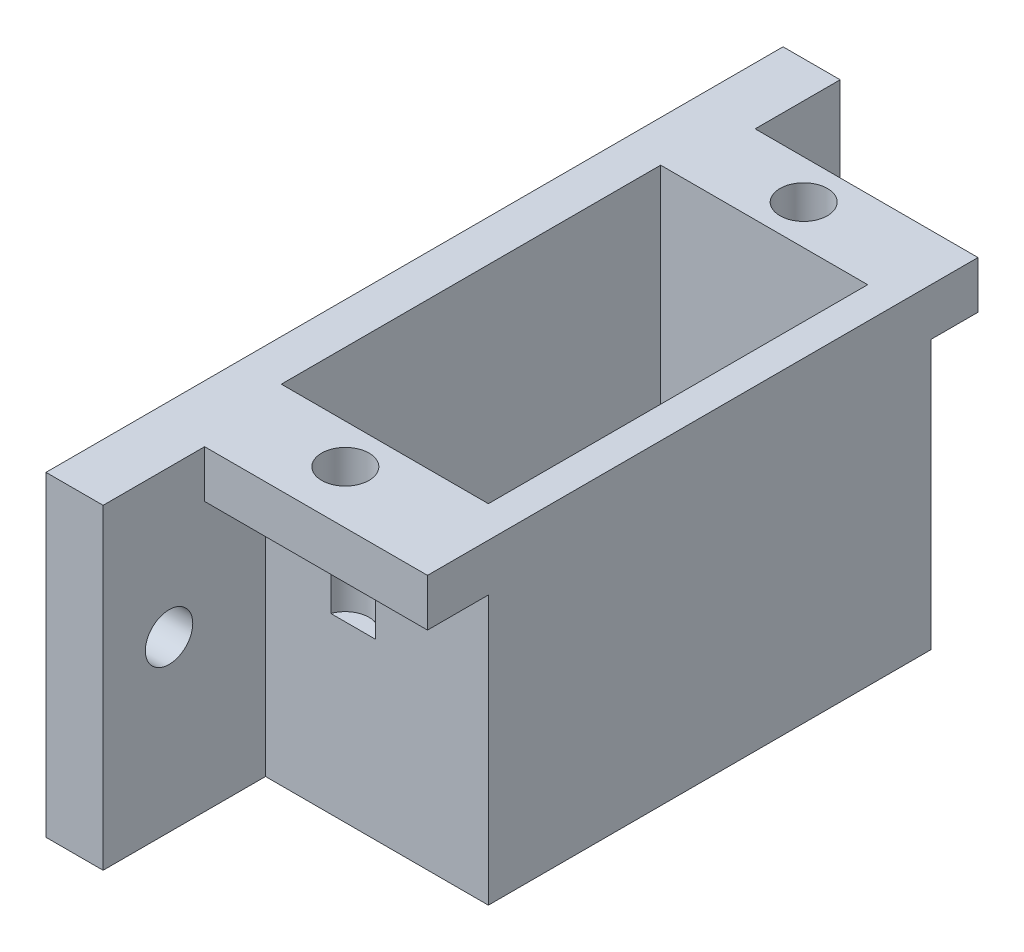
SolidWorks part; units mm, degrees
ref_plane "Płaszczyzna przednia" through (0, 0, 0) normal (0, 0, 1) x (1, 0, 0)
ref_plane "Płaszczyzna górna" through (0, 0, 0) normal (0, 1, 0) x (1, 0, 0)
ref_plane "Płaszczyzna prawa" through (0, 0, 0) normal (1, 0, 0) x (0, 0, -1)
sketch "Sketch1" plane through (0, 0, 0) normal (0, 1, 0) x (1, 0, 0)
  line L1 (51.8037, 18.5) -> (51.8037, 21.4784)
  line L3 (34.0907, 18.5) -> (37.7037, 18.5)
  line L4 (34.0907, 18.5) -> (34.0907, 26.8576)
  line L5 (34.0907, 26.8576) -> (37.7037, 26.8576)
  line L6 (34.0907, 18.5) -> (51.8037, 18.5)
  line L7 (36.7037, 16.5) -> (49.8037, 16.5)
  line L8 (36.7037, 16.5) -> (36.7037, -7.5)
  line L9 (36.7037, -7.5) -> (49.8037, -7.5)
  line L10 (49.8037, 16.5) -> (49.8037, -7.5)
  line L11 (51.8037, 18.5) -> (51.8037, -9.5)
  line L12 (34.0907, -9.5) -> (51.8037, -9.5)
  line L13 (34.0907, 18.5) -> (34.0907, -9.5)
  line L14 (37.7037, 18.5) -> (37.7037, 26.8576)
  line L15 (34.0907, -9.5) -> (37.7037, -9.5)
  line L16 (34.0907, -9.5) -> (34.0907, -19.7762)
  line L17 (34.0907, -19.7762) -> (37.7037, -19.7762)
  line L18 (37.7037, -9.5) -> (37.7037, -19.7762)
  line L19 (51.8037, 21.4784) -> (37.7037, 21.4784)
  line L20 (43.2537, 26.867) -> (43.2537, -20.3831) construction
  line L21 (51.8037, -9.5) -> (51.8037, -13.3519)
  line L22 (51.8037, -13.3519) -> (37.7037, -13.3519)
  circle A0 centre (43.2537, 19) radius 1.5
  circle A1 centre (43.2537, -10) radius 1.5
  dimension "D1" = 3
  dimension "D2" = 2.5
  dimension "D3" = 3
  dimension "D5" = 13.1
  dimension "D6" = 24
  dimension "D4" = 2.5
extrude "Boss-Extrude1" add sketch "Sketch1" along normal blind 20 contours L3 L13 L12 L11 L6 L7 L10 L9 L8 | L18 L12 L16 L17 | L3 L14 L5 L4 | A0 L20 L7 L10 L9 A1 L12 L11 L6 region at (51.5109, 0, -4.5) region at (36.4763, 0, -4.5) region at (35.8972, 0, -22.6788) region at (35.8972, 0, 14.6381)
sketch "Sketch4" plane through (37.7037, 0, 0) normal (1, 0, 0) x (0, 0, -1)
  circle A0 centre (-15.6035, 10.6942) radius 1.5
  circle A1 centre (22.5684, 10.2862) radius 1.5
  dimension "D1" = 3
  dimension "D2" = 3
extrude "Cut-Extrude1" cut sketch "Sketch4" along normal through all both and the other way through all
extrude "Boss-Extrude2" add sketch "Sketch1<31>" against normal blind 3 from surface contours A1 L20 L22 L21 L12 | L20 A1 L12 L18 L22 | L19 L20 A0 L6 L1 | L20 L19 L14 L6 A0 region at (47.9221, 0, -20.056) region at (47.8256, 0, 11.5123) region at (40.1023, 0, -20.0985) region at (40.199, 0, 11.5651) starting at face at (43.2537, 20, -4.5)
sketch "Sketch1<31>" plane through (0, 0, 0) normal (0, 1, 0) x (1, 0, 0) same geometry as "Sketch1"
extrude "Boss-Extrude3" add sketch "Sketch1<32>" along normal blind 11 contours L6 L20 A0 | L20 L6 A0 | L20 A1 L12 | A1 L20 L12 region at (43.8193, 0, -18.0858) region at (42.6881, 0, -18.0858) region at (43.8193, 0, 9.0858) region at (42.6881, 0, 9.0858)
sketch "Sketch1<32>" plane through (0, 0, 0) normal (0, 1, 0) x (1, 0, 0) same geometry as "Sketch1"
